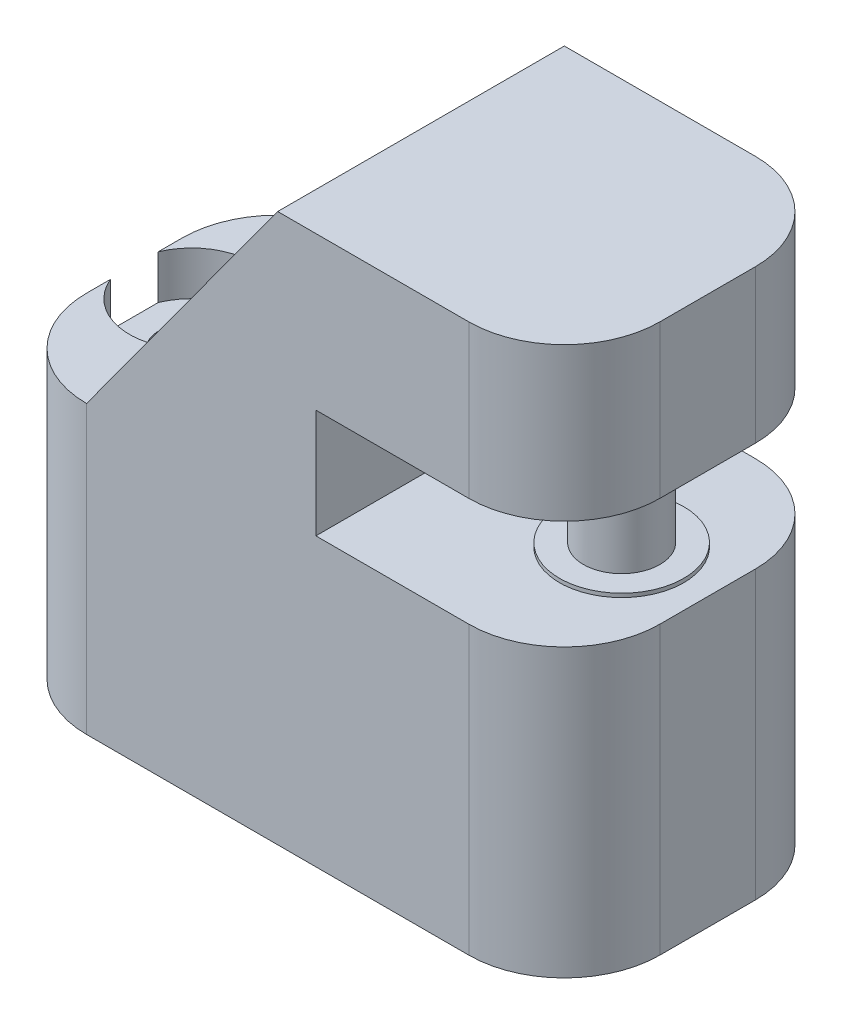
SolidWorks part; units mm, degrees
ref_plane "Front Plane" through (0, 0, 0) normal (0, 0, 1) x (1, 0, 0)
ref_plane "Top Plane" through (0, 0, 0) normal (0, 1, 0) x (1, 0, 0)
ref_plane "Right Plane" through (0, 0, 0) normal (1, 0, 0) x (0, 0, -1)
sketch "Sketch1" plane through (0, 0, 0) normal (0, 0, 1) x (1, 0, 0)
  line L0 (0, 0) -> (0, 15)
  line L1 (0, 15) -> (5, 15)
  line L2 (5, 15) -> (15, 28.7)
  line L3 (15, 28.7) -> (30, 28.7)
  line L4 (30, 28.7) -> (30, 20.7)
  line L5 (30, 20.7) -> (17, 20.7)
  line L6 (17, 20.7) -> (17, 15)
  line L7 (17, 15) -> (30, 15)
  line L8 (30, 15) -> (30, 0)
  line L9 (30, 0) -> (0, 0)
  point P11 (9.311, 10.8955)
  point P12 (15, 7.3568)
  dimension "D1" = 13
  dimension "D2" = 5.7
  dimension "D3" = 30
  dimension "D5" = 8
  dimension "D6" = 15
  dimension "D7" = 5
  dimension "D8" = 15
extrude "Boss-Extrude1" add sketch "Sketch1" along normal blind 15
ref_plane "Plane1" through (0, 17.85, 0) normal (0, 1, 0) x (1, 0, 0)
sketch "Sketch3" plane through (0, 15, 0) normal (0, 1, 0) x (1, 0, 0)
  line L0 (30, -15) -> (30, 0) construction
  line L1 (17, -15) -> (17, 0) construction
  circle A0 centre (25.5, -7.5) radius 2
  circle A1 centre (25.5, -7.5) radius 6.5 construction
  point P4 (30, -7.5)
  dimension "D1" = 4
  dimension "D2" = 8.5
  dimension "D3" = 13
extrude "Boss-Extrude2" add sketch "Sketch3" along normal up to next
sketch "Sketch4" plane through (0, 15, 0) normal (0, 1, 0) x (1, 0, 0)
  circle A0 centre (25.5, -7.5) radius 3.25
  dimension "D1" = 6.5
extrude "Boss-Extrude3" add sketch "Sketch4" along normal blind 0.2
mirror "Mirror1" about plane through (0, 17.85, 0) normal (0, 1, 0) of "Boss-Extrude3"
fillet "Fillet1" radius 5 6 edges at (30, 24.7, 0) (30, 24.7, 15) (30, 7.5, 0) (30, 7.5, 15) (0, 7.5, 0) (0, 7.5, 15)
sketch "Sketch5" plane through (0, 28.7, 0) normal (0, 1, 0) x (1, 0, 0)
  line L0 (0, -10) -> (0, -5) construction
  point P0 (3, -7.5)
  point P1 (10, -7.5)
  point P4 (0, -7.5)
  point P5 (0, 0)
  dimension "D1" = 7
  dimension "D2" = 3
hole_wizard "CBORE for M3 SHCS1" positions "Sketch5" profile "Sketch6" counterbore size "M3" standard "ANSI Metric" end condition through all
sketch "Sketch6" plane through (3, 28.7, 7.5) normal (1, 0, 0) x (0, 0, 1)
  line L0 (0, 0) -> (0, 28.7)
  line L1 (0, 28.7) -> (1.7, 28.7)
  line L3 (1.7, 28.7) -> (1.7, 16)
  line L4 (3.25, 16) -> (1.7, 16)
  line L5 (3.25, 16) -> (3.25, 0.025)
  line L6 (3.25, 0.025) -> (3.275, 0)
  line L7 (3.275, 0) -> (0, 0)
  line L8 (-3.25, 0.025) -> (-3.275, 0) construction
  line L11 (0, -6.35) -> (0, 107.95) construction
  dimension "Thru Hole Dia." = 3.4
  dimension "Thru Hole Depth" = 28.7
  dimension "C'Bore Dia." = 6.5
  dimension "C'Bore Depth" = 16
  dimension "Near C'Sink Dia." = 6.55
  dimension "Near C'Sink Angle" = 90
